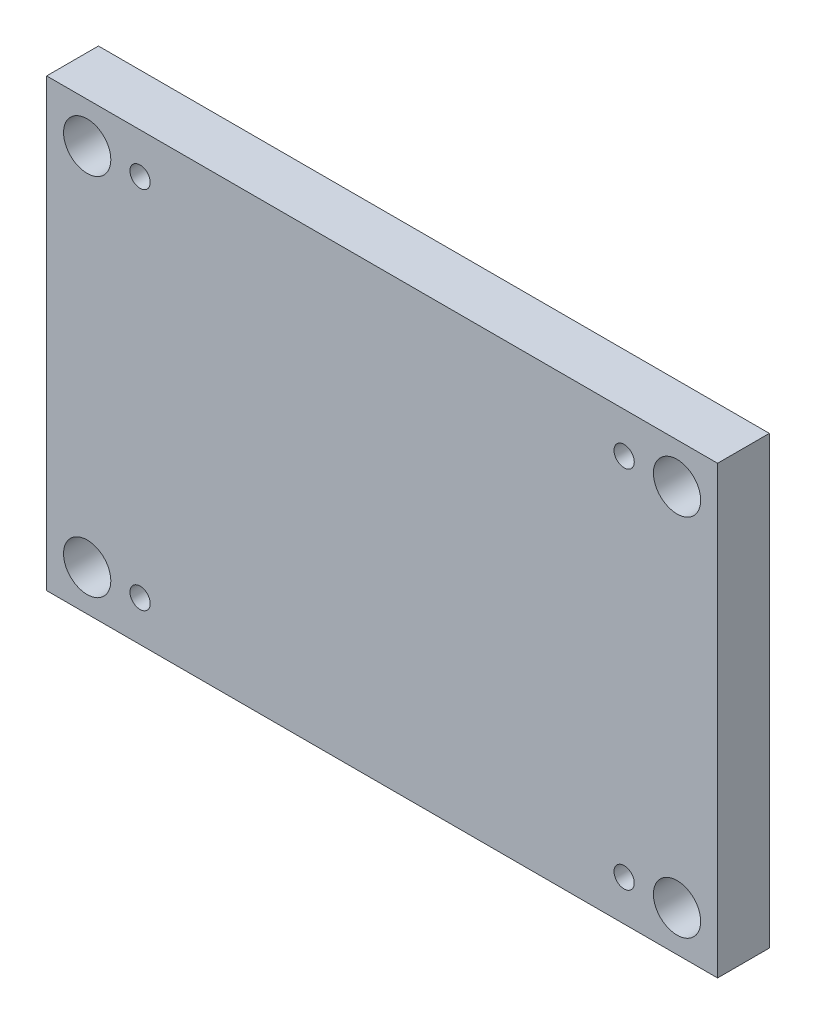
SolidWorks part; units mm, degrees
ref_plane "Płaszczyzna przednia" through (0, 0, 0) normal (0, 0, 1) x (1, 0, 0)
ref_plane "Płaszczyzna górna" through (0, 0, 0) normal (0, 1, 0) x (1, 0, 0)
ref_plane "Płaszczyzna prawa" through (0, 0, 0) normal (1, 0, 0) x (0, 0, -1)
sketch "Szkic1" plane through (0, 0, 0) normal (0, 0, 1) x (1, 0, 0)
  line L0 (-298, -198) -> (298, -198)
  line L1 (298, -198) -> (298, 198)
  line L2 (298, 198) -> (-298, 198)
  line L3 (-298, 198) -> (-298, -198)
extrude "Dodanie-wyciągnięcie1" add sketch "Szkic1" along normal blind 46
ref_plane "Płaszczyzna1" through (0, 0, 46) normal (0, 0, 1) x (1, 0, 0)
sketch "Szkic2" plane through (0, 0, 46) normal (0, 0, 1) x (1, 0, 0)
  circle A0 centre (262, 162) radius 21
extrude "Wytnij-wyciągnięcie1" cut sketch "Szkic2" against normal blind 46
sketch "Szkic3" plane through (0, 0, 46) normal (0, 0, 1) x (1, 0, 0)
  circle A0 centre (262, -162) radius 21
extrude "Wytnij-wyciągnięcie2" cut sketch "Szkic3" against normal blind 46
sketch "Szkic4" plane through (0, 0, 46) normal (0, 0, 1) x (1, 0, 0)
  circle A0 centre (-262, -162) radius 21
extrude "Wytnij-wyciągnięcie3" cut sketch "Szkic4" against normal blind 46
sketch "Szkic5" plane through (0, 0, 46) normal (0, 0, 1) x (1, 0, 0)
  circle A0 centre (-262, 162) radius 21
extrude "Wytnij-wyciągnięcie4" cut sketch "Szkic5" against normal blind 46
ref_plane "Płaszczyzna2" through (215, 0, 0) normal (1, 0, 0) x (0, 0, -1)
sketch "Szkic6" plane through (215, 0, 0) normal (1, 0, 0) x (0, 0, -1)
  line L0 (-46, 162) -> (-46, 171)
  line L1 (-46, 171) -> (0, 171)
  line L2 (0, 171) -> (0, 162)
  line L3 (0, 162) -> (-46, 162)
  line L4 (0, 162) -> (-46, 162) construction
revolve "Wycięcie-obrót1" cut sketch "Szkic6" angle 360 about L4 reverse direction yes
sketch "Szkic7" plane through (215, 0, 0) normal (1, 0, 0) x (0, 0, -1)
  line L0 (0, -162) -> (0, -171)
  line L1 (0, -171) -> (-46, -171)
  line L2 (-46, -171) -> (-46, -162)
  line L3 (-46, -162) -> (0, -162)
  line L4 (-46, -162) -> (0, -162) construction
revolve "Wycięcie-obrót2" cut sketch "Szkic7" angle 360 about L4 reverse direction yes
ref_plane "Płaszczyzna3" through (-215, 0, 0) normal (1, 0, 0) x (0, 0, -1)
sketch "Szkic8" plane through (-215, 0, 0) normal (1, 0, 0) x (0, 0, -1)
  line L0 (-46, 162) -> (-46, 171)
  line L1 (-46, 171) -> (0, 171)
  line L2 (0, 171) -> (0, 162)
  line L3 (0, 162) -> (-46, 162)
  line L4 (0, 162) -> (-46, 162) construction
revolve "Wycięcie-obrót3" cut sketch "Szkic8" angle 360 about L4 reverse direction yes
sketch "Szkic9" plane through (-215, 0, 0) normal (1, 0, 0) x (0, 0, -1)
  line L0 (0, -162) -> (0, -171)
  line L1 (0, -171) -> (-46, -171)
  line L2 (-46, -171) -> (-46, -162)
  line L3 (-46, -162) -> (0, -162)
  line L4 (-46, -162) -> (0, -162) construction
revolve "Wycięcie-obrót4" cut sketch "Szkic9" angle 360 about L4 reverse direction yes
ref_plane "IP1 XY" through (0, 0, 46) normal (0, 0, 1) x (1, 0, 0)
ref_plane "IP1 XZ" through (0, 0, 0) normal (0, -1, 0) x (-1, 0, 0)
ref_plane "IP1 YZ" through (0, 0, 0) normal (1, 0, 0) x (0, 0, -1)
ref_axis "IP1 X" through (-80.9, 0, 46) along (1, 0, 0)
ref_axis "IP1 Y" through (0, -50, 46) along (0, 1, 0)
ref_axis "IP1 Z" through (0, 0, 80.9) along (0, 0, -1)
sketch3d "IP1"
  point P0 (0, 0, 46)
